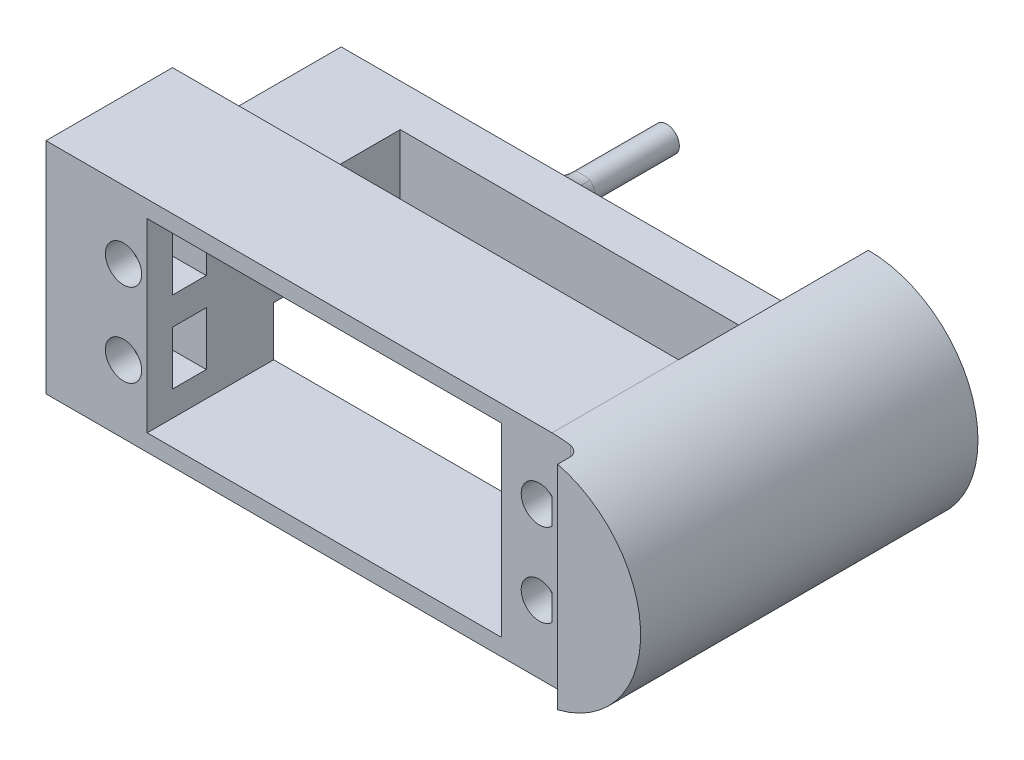
SolidWorks part; units mm, degrees
ref_plane "Plan de face" through (0, 0, 0) normal (0, 0, 1) x (1, 0, 0)
ref_plane "Plan de dessus" through (0, 0, 0) normal (0, 1, 0) x (1, 0, 0)
ref_plane "Plan de droite" through (0, 0, 0) normal (1, 0, 0) x (0, 0, -1)
sketch "Esquisse1" plane through (0, 0, 0) normal (0, 0, 1) x (1, 0, 0)
  line L1 (30, -13) -> (-30, -13)
  line L3 (30, 13) -> (-30, 13)
  line L4 (-30, -13) -> (-30, 13)
  line L5 (30, -13) -> (-30, 13) construction
  line L6 (30, 13) -> (-30, -13) construction
  arc A0 (30, -13) -> (30, 13) centre (30, 0) ccw
  point P0 (0, 0)
  dimension "D1" = 60
  dimension "D2" = 26
extrude "Boss.-Extru.1" add sketch "Esquisse1" along normal blind 15
sketch "Esquisse2" plane through (0, 0, 15) normal (0, 0, 1) x (1, 0, 0)
  line L0 (-30, 13) -> (-30, -13) construction
  line L1 (-18, 11) -> (24, 11)
  line L2 (-18, 11) -> (-18, -11)
  line L3 (-18, -11) -> (24, -11)
  line L4 (24, 11) -> (24, -11)
  point P4 (-18, 0)
  dimension "D1" = 42
  dimension "D2" = 22
  dimension "D3" = 12
extrude "Enlèv. mat.-Extru.1" cut sketch "Esquisse2" against normal through all
sketch "Esquisse4" plane through (0, 0, 15) normal (0, 0, 1) x (1, 0, 0)
  circle A0 centre (-20.81, 4.935) radius 2.15
  circle A1 centre (-20.81, -4.935) radius 2.15
  circle A2 centre (28.49, 4.935) radius 2.15
  circle A3 centre (28.49, -4.935) radius 2.15
extrude "Enlèv. mat.-Extru.2" cut sketch "Esquisse4" against normal blind 3
sketch "Esquisse5" plane through (-18, 0, 0) normal (1, 0, 0) x (0, 0, -1)
  line L1 (-12, -8) -> (-8, -8)
  line L2 (-12, -8) -> (-12, -1.65)
  line L3 (-12, -1.65) -> (-8, -1.65)
  line L4 (-8, -8) -> (-8, -1.65)
  line L5 (-15, 11) -> (-15, -11) construction
  line L6 (0, -11) -> (-15, -11) construction
  line L7 (-16.3207, 0) -> (1.751, 0) construction
  line L8 (-12, 1.65) -> (-8, 1.65)
  line L9 (-8, 8) -> (-8, 1.65)
  line L10 (-12, 8) -> (-8, 8)
  line L11 (-12, 8) -> (-12, 1.65)
  dimension "D1" = 6.35
  dimension "D2" = 4
  dimension "D3" = 3
  dimension "D4" = 3
extrude "Enlèv. mat.-Extru.3" cut sketch "Esquisse5" against normal blind 6
sketch "Esquisse6" plane through (24, 0, 0) normal (-1, 0, 0) x (0, 0, 1)
  line L0 (15, -11) -> (15, 11) construction
  line L1 (12, 8) -> (8, 8)
  line L2 (12, 8) -> (12, 1.65)
  line L3 (12, 1.65) -> (8, 1.65)
  line L4 (8, 8) -> (8, 1.65)
  line L5 (0, 11) -> (15, 11) construction
  line L6 (16.3207, 0) -> (-2.2889, 0) construction
  line L7 (12, -1.65) -> (8, -1.65)
  line L8 (8, -8) -> (8, -1.65)
  line L9 (12, -8) -> (8, -8)
  line L10 (12, -8) -> (12, -1.65)
  dimension "D1" = 6.35
  dimension "D2" = 4
  dimension "D3" = 3
  dimension "D4" = 3
extrude "Enlèv. mat.-Extru.4" cut sketch "Esquisse6" against normal blind 8
sketch "Esquisse10" plane through (0, 0, 0) normal (0, 0, -1) x (-1, 0, 0)
  line L0 (30, 13) -> (30, -13) construction
  line L1 (18, 0) -> (30, 0) construction
  line L2 (18, 11) -> (18, -11) construction
  line L3 (-24, 0) -> (-43, 0) construction
  line L4 (30, -5.1328) -> (18, -5.1328)
  line L5 (30, -5.1328) -> (30, 5.1328)
  line L6 (30, 5.1328) -> (18, 5.1328)
  line L7 (18, -5.1328) -> (18, 5.1328)
  line L8 (30, -5.1328) -> (18, 5.1328) construction
  line L9 (30, 5.1328) -> (18, -5.1328) construction
  line L10 (-24, -11) -> (-24, 11) construction
  line L11 (-24, 5.1328) -> (-41.9438, 5.1328)
  line L12 (-24, -5.1328) -> (-41.9438, -5.1328)
  line L13 (-24, 5.1328) -> (-24, -5.1328)
  arc A0 (-30, 13) -> (-30, -13) centre (-30, 0) ccw construction
  arc A1 (-41.9438, 5.1328) -> (-41.9438, -5.1328) centre (-30, 0) ccw
  point P9 (24, 0)
extrude "Boss.-Extru.6" add sketch "Esquisse10" along normal blind 20
sketch "Esquisse11" plane through (0, 0, -20) normal (0, 0, -1) x (-1, 0, 0)
  line L1 (-24, 5.1328) -> (18, 5.1328)
  line L2 (-24, 5.1328) -> (-24, -5.1328)
  line L3 (-24, -5.1328) -> (18, -5.1328)
  line L4 (18, 5.1328) -> (18, -5.1328)
extrude "Boss.-Extru.7" add sketch "Esquisse11" against normal blind 5
sketch "Esquisse12" plane through (0, 0, -20) normal (0, 0, -1) x (-1, 0, 0)
  line L0 (-30, -13) -> (-30, 13)
  arc A0 (-30, 13) -> (-41.9438, 5.1328) centre (-30, 0) ccw construction
  arc A1 (-41.9438, 5.1328) -> (-41.9438, -5.1328) centre (-30, 0) ccw construction
  arc A2 (-41.9438, -5.1328) -> (-30, -13) centre (-30, 0) ccw construction
  arc A3 (-30, 13) -> (-41.9438, 5.1328) centre (-30, 0) ccw
  arc A4 (-41.9438, 5.1328) -> (-41.9438, -5.1328) centre (-30, 0) ccw
  arc A5 (-41.9438, -5.1328) -> (-30, -13) centre (-30, 0) ccw
extrude "Boss.-Extru.8" add sketch "Esquisse12" against normal blind 35 and the other way blind 2.5
sketch "Esquisse13" plane through (0, 0, 15) normal (0, 0, 1) x (1, 0, 0)
  circle A0 centre (36.0309, 4.6665) radius 1.55
  circle A1 centre (36.0309, -5.3335) radius 1.55
  dimension "D1" = 3.1
  dimension "D2" = 3.1
  dimension "D3" = 10
extrude "Enlèv. mat.-Extru.5" cut sketch "Esquisse13" against normal through all
sketch "Esquisse14" plane through (0, 0, 15) normal (0, 0, 1) x (1, 0, 0)
  line L0 (33.1601, 12.6101) -> (33.1601, -12.6101)
  arc A0 (30, -13) -> (30, 13) centre (30, 0) ccw construction
  arc A1 (33.1601, -12.6101) -> (33.1601, 12.6101) centre (30, 0) ccw
extrude "Boss.-Extru.9" add sketch "Esquisse14" along normal blind 2.5
fillet "Congé1" radius 1 1 edges at (33.1601, 0, 15)
sketch "Esquisse15" plane through (0, 0, -20) normal (0, 0, -1) x (-1, 0, 0)
  circle A0 centre (6.41, 0) radius 1.5
  dimension "D1" = 3
extrude "Boss.-Extru.10" add sketch "Esquisse15" along normal blind 15
fillet "Congé2" radius 5 1 edges at (-7.91, 0, -20)
